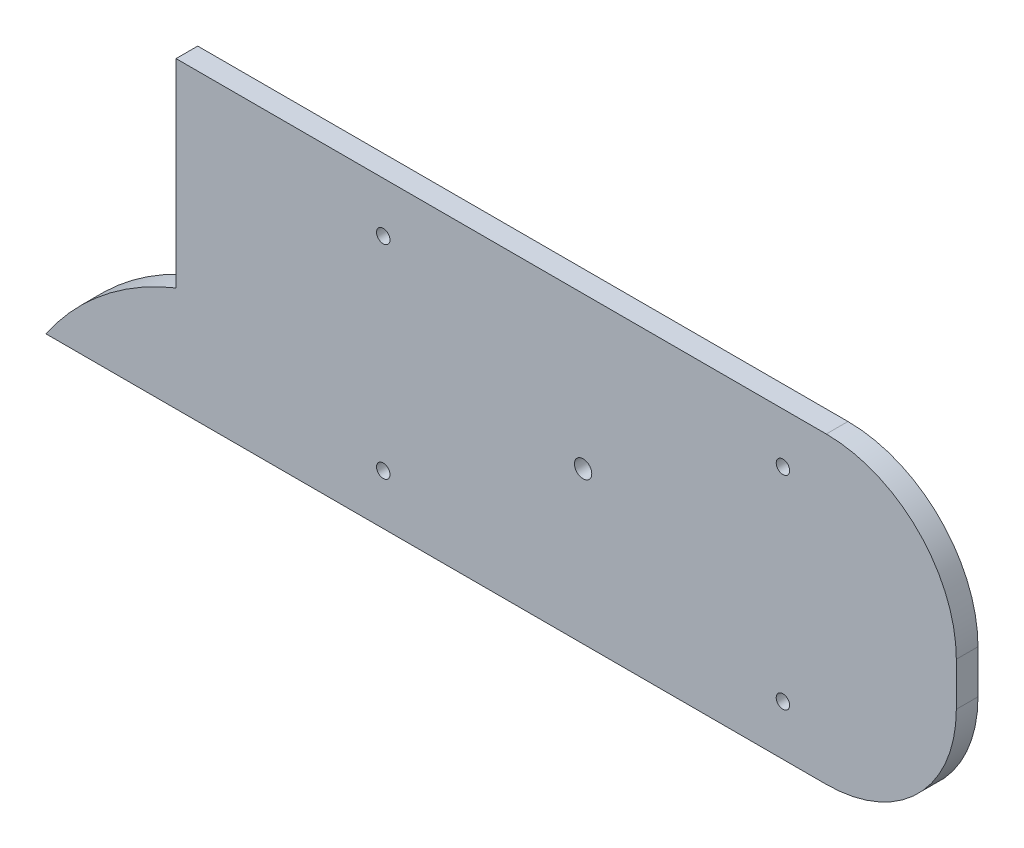
SolidWorks part; units mm, degrees
material "1060 Alloy"
ref_plane "Front Plane" through (0, 0, 0) normal (0, 0, 1) x (1, 0, 0)
ref_plane "Top Plane" through (0, 0, 0) normal (0, 1, 0) x (1, 0, 0)
ref_plane "Right Plane" through (0, 0, 0) normal (1, 0, 0) x (0, 0, -1)
sketch "Sketch2" plane through (0, 0, 0) normal (0, 0, 1) x (1, 0, 0)
  line L0 (0, 0) -> (457.2, 0)
  line L1 (76.2, 0) -> (76.2, 142.4009) construction
  line L2 (152.4, 0) -> (152.4, 186.487) construction
  line L9 (457.2, 177.8) -> (152.4, 177.8)
  line L14 (533.4, 76.2) -> (533.4, 101.6)
  line L15 (152.4, 177.8) -> (76.2, 177.8)
  line L16 (76.2, 177.8) -> (76.2, 61.4013)
  arc A5 (0, 0) -> (76.2, 61.4013) centre (138.3869, -93.7571) cw
  arc A6 (457.2, 0) -> (533.4, 76.2) centre (457.2, 76.2) ccw
  arc A7 (533.4, 101.6) -> (457.2, 177.8) centre (457.2, 101.6) ccw
  dimension "D6" = 167.1566
  dimension "D7" = 142.4009
  dimension "D5" = 177.8
  dimension "D1" = 76.2
  dimension "D4" = 457.2
  dimension "D9" = 138.3869
  dimension "D2" = 76.2
  dimension "D3" = 152.4
  dimension "D8" = 186.487
extrude "Boss-Extrude1" add sketch "Sketch2" along normal blind 12.7
sketch "Sketch4" plane through (0, 0, 12.7) normal (0, 0, 1) x (1, 0, 0)
  line L0 (314.706, 0) -> (314.706, 177.8) construction
  line L1 (0, 0) -> (457.2, 0) construction
  line L2 (457.2, 177.8) -> (76.2, 177.8) construction
  line L3 (76.2, 88.9) -> (533.4, 88.9) construction
  line L4 (76.2, 177.8) -> (76.2, 61.4013) construction
  line L6 (533.4, 76.2) -> (533.4, 101.6) construction
  circle A0 centre (314.706, 88.9) radius 5.08
  circle A3 centre (431.8, 148.4376) radius 3.937
  circle A5 centre (197.612, 148.4376) radius 3.937
  circle A6 centre (197.612, 29.3624) radius 3.937
  circle A7 centre (431.8, 29.3624) radius 3.937
  dimension "D1" = 10.16
  dimension "D4" = 7.874
  dimension "D5" = 29.3624
  dimension "D6" = 117.094
  dimension "D2" = 314.706
  dimension "D3" = 88.9
extrude "Cut-Extrude2" cut sketch "Sketch4" against normal through all
equation "\"0.5n\"=0.25"
equation "\".5n\"=0.25"
